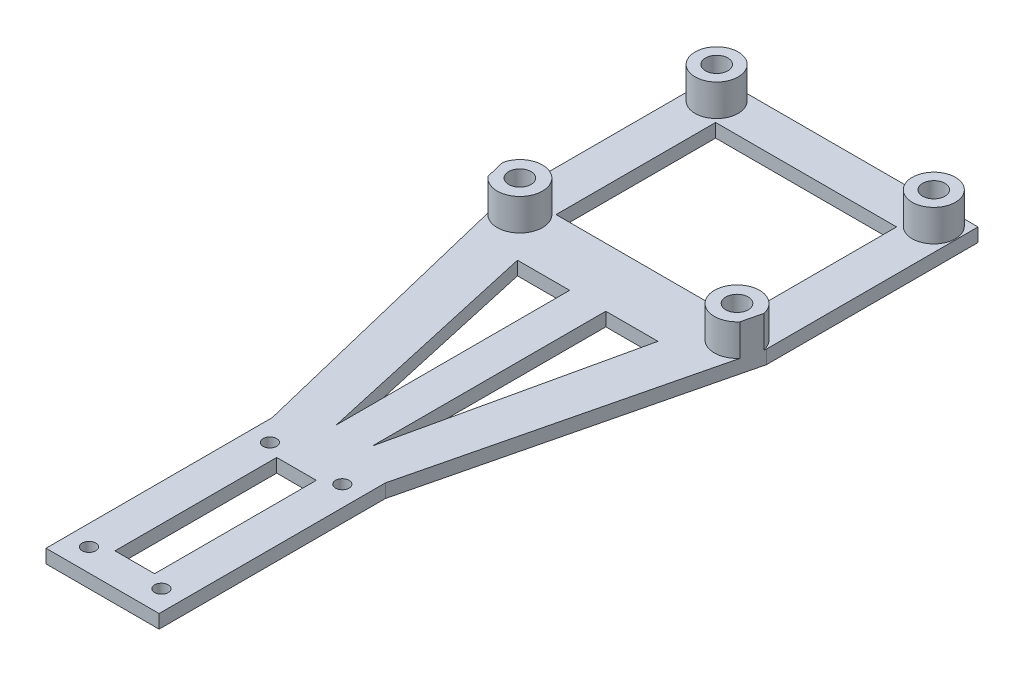
SolidWorks part; units mm, degrees
ref_plane "Front Plane" through (0, 0, 0) normal (0, 0, 1) x (1, 0, 0)
ref_plane "Top Plane" through (0, 0, 0) normal (0, 1, 0) x (1, 0, 0)
ref_plane "Right Plane" through (0, 0, 0) normal (1, 0, 0) x (0, 0, -1)
sketch "Sketch2" plane through (0, 0, 0) normal (0, 1, 0) x (1, 0, 0)
  line L0 (6, -45) -> (19, -45)
  line L1 (0, 0) -> (25, 0)
  line L2 (0, 0) -> (0, -50)
  line L3 (0, -50) -> (25, -50)
  line L4 (25, 0) -> (25, -50)
  line L5 (16.5, 57.25) -> (28.0289, 57.25)
  line L6 (28.0289, 57.25) -> (16.5, 5.6281)
  line L7 (16.5, 5.6281) -> (16.5, 57.25)
  line L8 (0, -25) -> (25, -25)
  line L9 (19, -45) -> (19, -5)
  line L10 (19, -5) -> (6, -5)
  line L11 (6, -5) -> (6, -45)
  line L12 (-3.0289, 57.25) -> (8.5, 5.6281)
  line L13 (8.5, 57.25) -> (-3.0289, 57.25)
  line L14 (-11.5, 109.75) -> (36.5, 109.75)
  line L15 (8.1213, -7.1213) -> (16.8787, -7.1213)
  line L16 (8.1213, -7.1213) -> (8.1213, -42.8787)
  line L17 (8.1213, -42.8787) -> (16.8787, -42.8787)
  line L18 (16.8787, -7.1213) -> (16.8787, -42.8787)
  line L19 (8.5, 5.6281) -> (8.5, 57.25)
  line L20 (12.5, 0) -> (12.5, 109.75)
  line L21 (36.5, 88) -> (-11.5, 88)
  line L24 (41.5, 67.7856) -> (25, 0)
  line L25 (41.5, 114.5227) -> (-16.5, 114.5227)
  line L26 (41.5, 114.5227) -> (41.5, 67.7856)
  line L28 (-16.5, 114.5227) -> (-16.5, 67.7856)
  line L29 (25, 0) -> (0, 0)
  line L33 (0, 0) -> (-16.5, 67.7856)
  line L36 (-8.8822, 61.25) -> (-14.9091, 61.25)
  line L37 (32.5, 105.5227) -> (-7.5, 105.5227)
  line L38 (32.5, 105.5227) -> (32.5, 70.25)
  line L39 (32.5, 70.25) -> (-7.5, 70.25)
  line L40 (-7.5, 105.5227) -> (-7.5, 70.25)
  line L42 (-8.8822, 61.25) -> (33.0872, 61.25)
  line L43 (33.0872, 61.25) -> (19.336, 0)
  line L44 (19.336, 0) -> (6, 0)
  line L45 (6, 0) -> (-8.8822, 61.25)
  line L46 (33.0872, 61.25) -> (39.9091, 61.25)
  circle A0 centre (4.5, -45) radius 1.5
  circle A1 centre (20.5, -45) radius 1.5
  circle A2 centre (20.5, -5) radius 1.5
  circle A3 centre (4.5, -5) radius 1.5
  circle A4 centre (36.5, 109.75) radius 2.475
  circle A5 centre (-11.5, 109.75) radius 2.475
  circle A6 centre (-11.5, 66.25) radius 2.475
  circle A7 centre (36.5, 66.25) radius 2.475
  circle A14 centre (-11.5, 109.75) radius 4.7727
  circle A15 centre (36.5, 109.75) radius 4.7727
  circle A16 centre (-11.5, 66.25) radius 5
  circle A17 centre (36.5, 66.25) radius 5
  point P32 (12.5, 109.75)
  dimension "D5" = 37
  dimension "D6" = 3
  dimension "D4" = 9
  dimension "D9" = 43.5
  dimension "D11" = 29
  dimension "D13" = 4.95
  dimension "D14" = 4.95
  dimension "D15" = 4.95
  dimension "D16" = 4.95
  dimension "D17" = 4.7727
  dimension "D21" = 0
  dimension "D1" = 50
  dimension "D2" = 9
  dimension "D3" = 9
  dimension "D7" = 3
  dimension "D8" = 48
  dimension "D10" = 9
  dimension "D12" = 29
  dimension "D18" = 4
  dimension "D19" = 4
  dimension "D20" = 4
extrude "Boss-Extrude1" add sketch "Sketch2" along normal blind 3 contours L46 L43 L29 L24 | L1 L45 L36 L33 | L45 L29 L20 L42 L19 L12 L13 | L43 L42 L20 L1 L6 L7 L5 | A16 L36 L42 L20 L39 L40 L37 L14 A14 L25 L28 L33 | A17 L24 L26 L25 A15 L14 L20 L37 L38 L39 L42 L46 | A6 | A16 L33 A6 | A17 L24 A7 | A7 | A17 L46 L24 | A16 L33 L36 | L11 A3 L10 A2 L9 L8 L4 L29 L1 L2 | L9 A1 L0 A0 L11 L8 L2 L3 L4 | L15 L18 L8 L9 L10 L11 L16 | L8 L18 L17 L16 L11 L0 L9 | A15 L25 A14 L14 | A5 | A14 A5 | A4 | A15 A4 region at (6.2385, 0, 35) region at (12.5, 0, 45.3536) region at (6.2385, 0, 15) region at (3, 0, 24.6464) region at (-4.4534, 0, -30.6478) region at (29.5546, 0, -31.5717) region at (-0.8107, 0, -30.7782) region at (-14.2458, 0, -61.7514) region at (15.918, 0, -0.6462) region at (39.2458, 0, -61.7514) region at (-10.1911, 0, -61.3107) region at (-15.7308, 0, -65.2202) region at (22.7936, 0, -61.8565) region at (38.5669, 0, -61.8521) region at (12.5, 0, -112.2031) region at (-13.905, 0, -109.75) region at (-8.2207, 0, -113.0293) region at (36.5, 0, -112.155) region at (39.7793, 0, -113.0293) region at (-11.5, 0, -66.25) region at (36.5, 0, -66.25)
extrude "Boss-Extrude2" add sketch "Sketch2<4>" along normal blind 6 contours A16 A6 | A14 A5 | A15 A4 | A17 A7 | A7 | A6 | A5 | A4 region at (-15.7308, 0, -65.2202) region at (38.5669, 0, -61.8521) region at (-13.905, 0, -109.75) region at (-8.2207, 0, -113.0293) region at (36.5, 0, -112.155) region at (39.7793, 0, -113.0293) region at (-11.5, 0, -66.25) region at (36.5, 0, -66.25)
sketch "Sketch2<4>" plane through (0, 0, 0) normal (0, 1, 0) x (1, 0, 0) same geometry as "Sketch2"
extrude "Boss-Extrude3" add sketch "Sketch2<5>" along normal blind 10 contours A14 A5 | A15 A4 | A16 L33 A6 | A17 L24 A7 region at (-15.7308, 0, -65.2202) region at (38.5669, 0, -61.8521) region at (-8.2207, 0, -113.0293) region at (39.7793, 0, -113.0293)
sketch "Sketch2<5>" plane through (0, 0, 0) normal (0, 1, 0) x (1, 0, 0) same geometry as "Sketch2"
